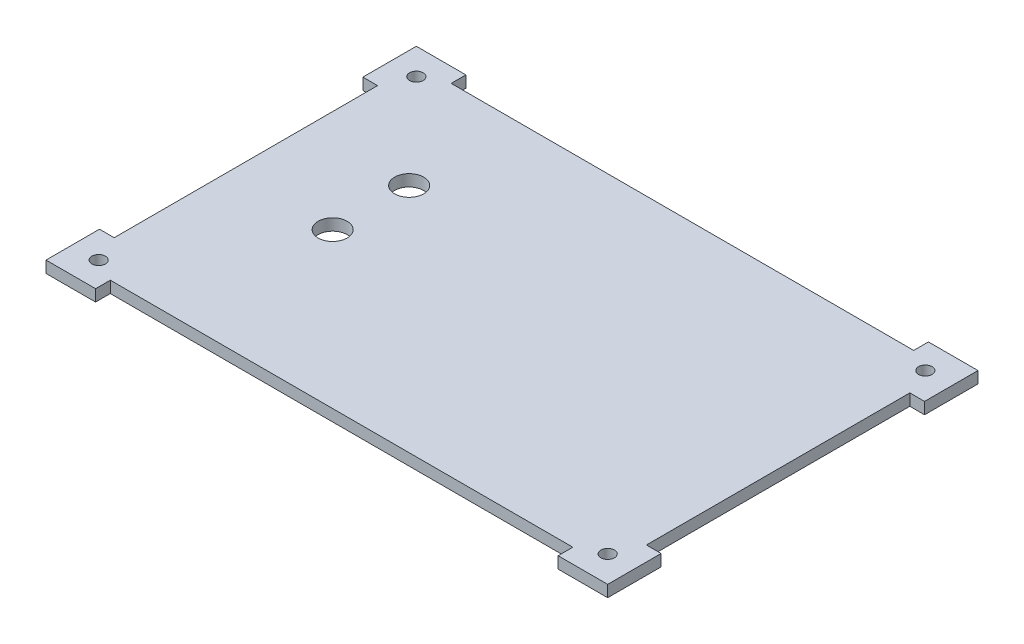
SolidWorks part; units mm, degrees
ref_plane "Front Plane" through (0, 0, 0) normal (0, 0, 1) x (1, 0, 0)
ref_plane "Top Plane" through (0, 0, 0) normal (0, 1, 0) x (1, 0, 0)
ref_plane "Right Plane" through (0, 0, 0) normal (1, 0, 0) x (0, 0, -1)
sketch "Sketch1" plane through (0, 0, 0) normal (0, 1, 0) x (1, 0, 0)
  line L1 (0, 0) -> (137.4, 0)
  line L2 (0, 0) -> (0, -88)
  line L3 (0, -88) -> (137.4, -88)
  line L4 (137.4, 0) -> (137.4, -88)
  dimension "D1" = 137.4
  dimension "D2" = 88
extrude "Boss-Extrude1" add sketch "Sketch1" along normal blind 3
sketch "Sketch2" plane through (0, 0, 0) normal (0, -1, 0) x (1, 0, 0)
  line L0 (0, 0) -> (0, 88) construction
  line L1 (0, 88) -> (137.4, 88) construction
  line L2 (137.4, 0) -> (0, 0) construction
  line L3 (137.4, 88) -> (137.4, 0) construction
  circle A0 centre (3, 85) radius 1.75
  circle A1 centre (134.4, 85) radius 1.75
  circle A2 centre (134.4, 3) radius 1.75
  circle A3 centre (3, 3) radius 1.75
  dimension "D1" = 3.5
  dimension "D2" = 3
  dimension "D3" = 3
  dimension "D4" = 3
  dimension "D5" = 3
  dimension "D6" = 3
  dimension "D7" = 3
  dimension "D8" = 3
  dimension "D9" = 3
extrude "Cut-Extrude1" cut sketch "Sketch2" against normal through all
sketch "Sketch3" plane through (0, 0, 0) normal (0, -1, 0) x (1, 0, 0)
  line L0 (0, 0) -> (0, 88) construction
  line L1 (-3.8, 91.8) -> (0, 91.8)
  line L2 (-3.8, 91.8) -> (-3.8, 78)
  line L3 (-3.8, 78) -> (0, 78)
  line L4 (0, 91.8) -> (0, 78)
  line L5 (0, 88) -> (137.4, 88) construction
  line L6 (0, 91.8) -> (9, 91.8)
  line L7 (0, 91.8) -> (0, 88)
  line L8 (0, 88) -> (9, 88)
  line L9 (9, 91.8) -> (9, 88)
  line L10 (137.4, 88) -> (137.4, 0) construction
  line L11 (137.4, 88) -> (128.4, 88)
  line L12 (137.4, 88) -> (137.4, 91.8)
  line L13 (137.4, 91.8) -> (128.4, 91.8)
  line L14 (128.4, 88) -> (128.4, 91.8)
  line L15 (137.4, 91.8) -> (141.2, 91.8)
  line L16 (137.4, 91.8) -> (137.4, 78)
  line L17 (137.4, 78) -> (141.2, 78)
  line L18 (141.2, 91.8) -> (141.2, 78)
  line L19 (137.4, 0) -> (0, 0) construction
  line L20 (0, 0) -> (-3.8, 0)
  line L21 (0, 0) -> (0, 10)
  line L22 (0, 10) -> (-3.8, 10)
  line L23 (-3.8, 0) -> (-3.8, 10)
  line L24 (-3.8, 0) -> (9, 0)
  line L25 (-3.8, 0) -> (-3.8, -3.8)
  line L26 (-3.8, -3.8) -> (9, -3.8)
  line L27 (9, 0) -> (9, -3.8)
  line L29 (137.4, 0) -> (141.2, 0)
  line L30 (137.4, 0) -> (137.4, 10)
  line L31 (137.4, 10) -> (141.2, 10)
  line L32 (141.2, 0) -> (141.2, 10)
  line L33 (141.2, 0) -> (128.4, 0)
  line L34 (141.2, 0) -> (141.2, -3.8)
  line L35 (141.2, -3.8) -> (128.4, -3.8)
  line L36 (128.4, 0) -> (128.4, -3.8)
  line M11 (0, 88) -> (0, 0)
  line M12 (0, 0) -> (137.4, 0)
  line M13 (137.4, 0) -> (137.4, 88)
  line M14 (137.4, 88) -> (0, 88)
  dimension "D1" = 10
  dimension "D2" = 9
  dimension "D3" = 3.8
  dimension "D4" = 3.8
  dimension "D5" = 3.8
  dimension "D6" = 3.8
  dimension "D7" = 9
  dimension "D8" = 10
  dimension "D9" = 3.8
  dimension "D10" = 3.8
  dimension "D11" = 10
  dimension "D12" = 9
  dimension "D13" = 3.8
  dimension "D14" = 3.8
  dimension "D15" = 10
  dimension "D16" = 9
extrude "Boss-Extrude2" add sketch "Sketch3" against normal through all contours L4 L1 L2 L3 M11 | L9 L6 L4 M14 | L23 L20 L22 M11 | L27 L20 L25 L26 M12 | L36 L35 L34 L29 M12 | L29 L32 L31 M13 | L14 L12 L13 M14 | L18 L15 L12 L17 M13 region at (-1.9, 0, 84.9) region at (4.5, 0, 89.9) region at (-1.9, 0, 5) region at (132.9, 0, 89.9) region at (2.6, 0, -1.9) region at (139.3, 0, 84.9) region at (134.8, 0, -1.9) region at (139.3, 0, 5)
sketch "Sketch4" plane through (0, 0, 0) normal (0, -1, 0) x (1, 0, 0)
  line L0 (0, 10) -> (0, 78) construction
  line L1 (9, 88) -> (128.4, 88) construction
  circle A0 centre (26.4, 48) radius 3.75
  circle A1 centre (26.4, 28.25) radius 3.75
  dimension "D1" = 7.5
  dimension "D2" = 7.5
  dimension "D3" = 26.4
  dimension "D4" = 40
  dimension "D5" = 26.4
  dimension "D6" = 19.75
extrude "Cut-Extrude2" cut sketch "Sketch4" against normal through all
equation "\"D4@Sketch2\"=\"D2@Sketch2\""
equation "\"D5@Sketch2\"=\"D4@Sketch2\""
equation "\"D6@Sketch2\"=\"D5@Sketch2\""
equation "\"D7@Sketch2\"=\"D6@Sketch2\""
equation "\"D8@Sketch2\"=\"D2@Sketch2\""
equation "\"D9@Sketch2\"=\"D8@Sketch2\""
equation "\"D2@Sketch4\"=\"D1@Sketch4\""
equation "\"D5@Sketch4\"=\"D3@Sketch4\""
equation "\"D9@Sketch3\"=\"D3@Sketch3\""
equation "\"D4@Sketch3\"=\"D5@Sketch3\""
equation "\"D10@Sketch3\"=\"D5@Sketch3\""
equation "\"D14@Sketch3\"=\"D5@Sketch3\""
equation "\"D13@Sketch3\"=\"D6@Sketch3\""
